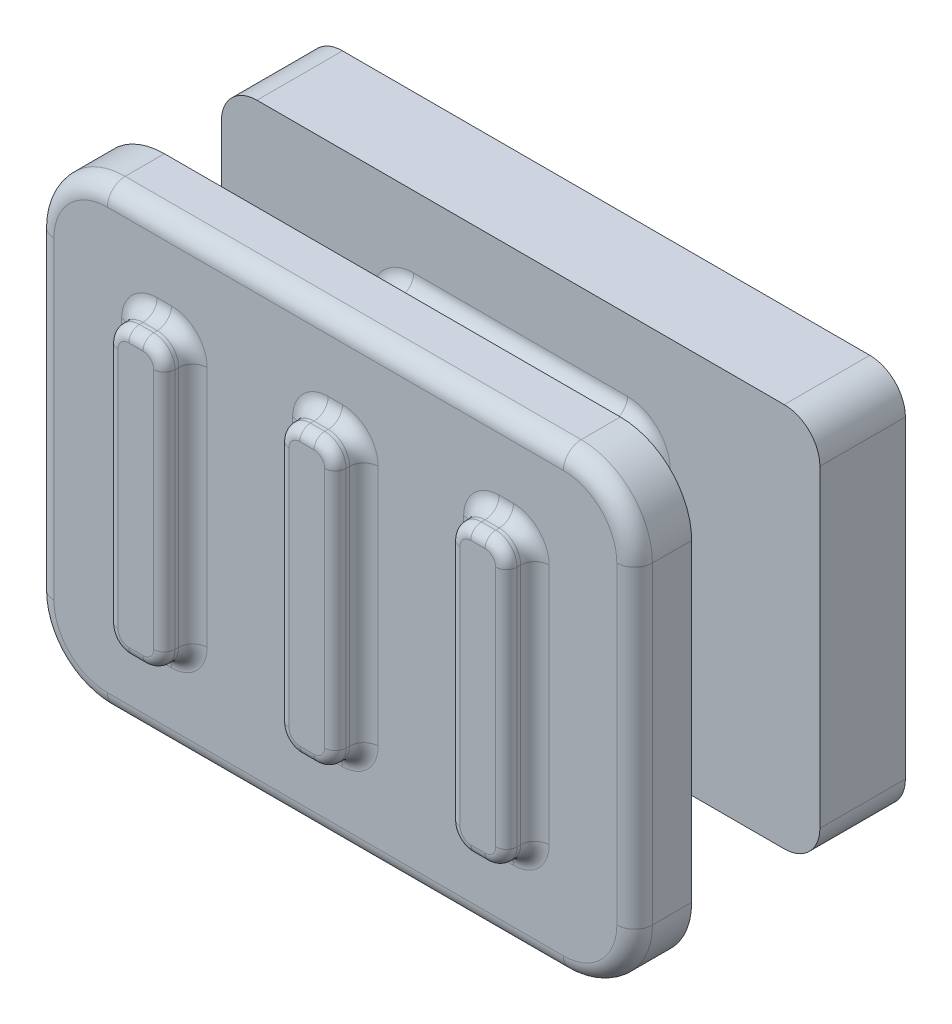
SolidWorks part; units mm, degrees
ref_plane "Спереди" through (0, 0, 0) normal (0, 0, 1) x (1, 0, 0)
ref_plane "Сверху" through (0, 0, 0) normal (0, 1, 0) x (1, 0, 0)
ref_plane "Справа" through (0, 0, 0) normal (1, 0, 0) x (0, 0, -1)
other "Configuration Table"
sketch "Slider_stem_profile" plane through (0, 0, 0) normal (0, 0, 1) x (1, 0, 0)
  line L0 (-1.5, -1.5) -> (1.5, -1.5)
  line L1 (1.9, -1.1) -> (1.9, 1.1)
  line L2 (1.5, 1.5) -> (-1.5, 1.5)
  line L3 (-1.9, 1.1) -> (-1.9, -1.1)
  arc A0 (1.5, -1.5) -> (1.9, -1.1) centre (1.5, -1.1) ccw
  arc A1 (1.9, 1.1) -> (1.5, 1.5) centre (1.5, 1.1) ccw
  arc A2 (-1.5, 1.5) -> (-1.9, 1.1) centre (-1.5, 1.1) ccw
  arc A3 (-1.9, -1.1) -> (-1.5, -1.5) centre (-1.5, -1.1) ccw
extrude "Slider_stem" add sketch "Slider_stem_profile" along normal blind 4.2 from offset 0
sketch "Captive_flange_profile" plane through (0, 0, 0) normal (0, 0, 1) x (1, 0, 0)
  line L0 (-3.7, -2.7) -> (3.7, -2.7)
  line L1 (4.2, -2.2) -> (4.2, 2.2)
  line L2 (3.7, 2.7) -> (-3.7, 2.7)
  line L3 (-4.2, 2.2) -> (-4.2, -2.2)
  arc A0 (3.7, -2.7) -> (4.2, -2.2) centre (3.7, -2.2) ccw
  arc A1 (4.2, 2.2) -> (3.7, 2.7) centre (3.7, 2.2) ccw
  arc A2 (-3.7, 2.7) -> (-4.2, 2.2) centre (-3.7, 2.2) ccw
  arc A3 (-4.2, -2.2) -> (-3.7, -2.7) centre (-3.7, -2.2) ccw
extrude "Captive_flange" add sketch "Captive_flange_profile" along normal blind 1.2 from offset 1.2
sketch "Thumb_pad_profile" plane through (0, 0, 0) normal (0, 0, 1) x (1, 0, 0)
  line L0 (-3.2, -3.2) -> (3.2, -3.2)
  line L1 (4.2, -2.2) -> (4.2, 2.2)
  line L2 (3.2, 3.2) -> (-3.2, 3.2)
  line L3 (-4.2, 2.2) -> (-4.2, -2.2)
  arc A0 (3.2, -3.2) -> (4.2, -2.2) centre (3.2, -2.2) ccw
  arc A1 (4.2, 2.2) -> (3.2, 3.2) centre (3.2, 2.2) ccw
  arc A2 (-3.2, 3.2) -> (-4.2, 2.2) centre (-3.2, 2.2) ccw
  arc A3 (-4.2, -2.2) -> (-3.2, -3.2) centre (-3.2, -2.2) ccw
extrude "Thumb_pad" add sketch "Thumb_pad_profile" along normal blind 0.8 from offset 4.2
sketch "Switch_pin_socket_profile" plane through (0, 0, 0) normal (0, 0, 1) x (1, 0, 0)
  line L0 (-0.8, -0.6) -> (0.8, -0.6)
  line L1 (0.9, -0.5) -> (0.9, 0.5)
  line L2 (0.8, 0.6) -> (-0.8, 0.6)
  line L3 (-0.9, 0.5) -> (-0.9, -0.5)
  arc A0 (0.8, -0.6) -> (0.9, -0.5) centre (0.8, -0.5) ccw
  arc A1 (0.9, 0.5) -> (0.8, 0.6) centre (0.8, 0.5) ccw
  arc A2 (-0.8, 0.6) -> (-0.9, 0.5) centre (-0.8, 0.5) ccw
  arc A3 (-0.9, -0.5) -> (-0.8, -0.6) centre (-0.8, -0.5) ccw
extrude "Switch_pin_socket" cut sketch "Switch_pin_socket_profile" against normal blind 2.4 from offset 2.3
sketch "PCB_edge_relief_profile" plane through (0, 0, 0) normal (0, 0, 1) x (1, 0, 0)
  line L0 (-2, 0.55) -> (2, 0.55)
  line L1 (2, 0.55) -> (2, 1.6)
  line L2 (2, 1.6) -> (-2, 1.6)
  line L3 (-2, 1.6) -> (-2, 0.55)
extrude "PCB_edge_relief" cut sketch "PCB_edge_relief_profile" against normal blind 0.7 from offset 0.6
fillet "Stem_shoulder_round" radius 0.2 24 edges at (1.7828, -1.3828, 1.2) (-1.7828, -1.3828, 1.2) (-1.7828, 1.3828, 1.2) (1.7828, 1.3828, 1.2) (1.7828, -1.3828, 2.4) (-1.7828, -1.3828, 2.4) (-1.7828, 1.3828, 2.4) (1.7828, 1.3828, 2.4) (-1.7828, -1.3828, 4.2) (-1.7828, 1.3828, 4.2) (1.7828, 1.3828, 4.2) (1.7828, -1.3828, 4.2) (0, 1.5, 1.2) (-1.9, 0, 1.2) (0, -1.5, 1.2) (1.9, 0, 1.2) (0, 1.5, 2.4) (-1.9, 0, 2.4) (0, -1.5, 2.4) (1.9, 0, 2.4) (1.9, 0, 4.2) (0, 1.5, 4.2) (-1.9, 0, 4.2) (0, -1.5, 4.2)
sketch "Thumb_rib_0_profile" plane through (0, 0, 0) normal (0, 0, 1) x (1, 0, 0)
  line L0 (-2.5, -2) -> (-2.3, -2)
  line L1 (-2, -1.7) -> (-2, 1.7)
  line L2 (-2.3, 2) -> (-2.5, 2)
  line L3 (-2.8, 1.7) -> (-2.8, -1.7)
  arc A0 (-2.3, -2) -> (-2, -1.7) centre (-2.3, -1.7) ccw
  arc A1 (-2, 1.7) -> (-2.3, 2) centre (-2.3, 1.7) ccw
  arc A2 (-2.5, 2) -> (-2.8, 1.7) centre (-2.5, 1.7) ccw
  arc A3 (-2.8, -1.7) -> (-2.5, -2) centre (-2.5, -1.7) ccw
extrude "Thumb_rib_0" add sketch "Thumb_rib_0_profile" along normal blind 0.5 from offset 4.9
sketch "Thumb_rib_1_profile" plane through (0, 0, 0) normal (0, 0, 1) x (1, 0, 0)
  line L0 (-0.1, -2) -> (0.1, -2)
  line L1 (0.4, -1.7) -> (0.4, 1.7)
  line L2 (0.1, 2) -> (-0.1, 2)
  line L3 (-0.4, 1.7) -> (-0.4, -1.7)
  arc A0 (0.1, -2) -> (0.4, -1.7) centre (0.1, -1.7) ccw
  arc A1 (0.4, 1.7) -> (0.1, 2) centre (0.1, 1.7) ccw
  arc A2 (-0.1, 2) -> (-0.4, 1.7) centre (-0.1, 1.7) ccw
  arc A3 (-0.4, -1.7) -> (-0.1, -2) centre (-0.1, -1.7) ccw
extrude "Thumb_rib_1" add sketch "Thumb_rib_1_profile" along normal blind 0.5 from offset 4.9
sketch "Thumb_rib_2_profile" plane through (0, 0, 0) normal (0, 0, 1) x (1, 0, 0)
  line L0 (2.3, -2) -> (2.5, -2)
  line L1 (2.8, -1.7) -> (2.8, 1.7)
  line L2 (2.5, 2) -> (2.3, 2)
  line L3 (2, 1.7) -> (2, -1.7)
  arc A0 (2.5, -2) -> (2.8, -1.7) centre (2.5, -1.7) ccw
  arc A1 (2.8, 1.7) -> (2.5, 2) centre (2.5, 1.7) ccw
  arc A2 (2.3, 2) -> (2, 1.7) centre (2.3, 1.7) ccw
  arc A3 (2, -1.7) -> (2.3, -2) centre (2.3, -1.7) ccw
extrude "Thumb_rib_2" add sketch "Thumb_rib_2_profile" along normal blind 0.5 from offset 4.9
fillet "Thumb_rib_root_round" radius 0.2 24 edges at (2.0879, -1.9121, 5) (2.4, -2, 5) (2.7121, -1.9121, 5) (2.7121, 1.9121, 5) (2.4, 2, 5) (2.0879, 1.9121, 5) (-0.3121, -1.9121, 5) (0, -2, 5) (0.3121, -1.9121, 5) (0.3121, 1.9121, 5) (0, 2, 5) (-0.3121, 1.9121, 5) (-2.7121, -1.9121, 5) (-2.4, -2, 5) (-2.0879, -1.9121, 5) (-2.0879, 1.9121, 5) (-2.4, 2, 5) (-2.7121, 1.9121, 5) (2.8, 0, 5) (2, 0, 5) (0.4, 0, 5) (-0.4, 0, 5) (-2, 0, 5) (-2.8, 0, 5)
fillet "Thumb_pad_edge_round" radius 0.25 8 edges at (-3.9071, -2.9071, 5) (-4.2, 0, 5) (0, -3.2, 5) (-3.9071, 2.9071, 5) (3.9071, -2.9071, 5) (0, 3.2, 5) (4.2, 0, 5) (3.9071, 2.9071, 5)
fillet "Thumb_rib_crown_round" radius 0.15 24 edges at (2.8, 0, 5.4) (2.7121, 1.9121, 5.4) (2.7121, -1.9121, 5.4) (2.4, 2, 5.4) (2.4, -2, 5.4) (2.0879, 1.9121, 5.4) (2.0879, -1.9121, 5.4) (2, 0, 5.4) (0.4, 0, 5.4) (0.3121, 1.9121, 5.4) (0.3121, -1.9121, 5.4) (0, 2, 5.4) (0, -2, 5.4) (-0.3121, 1.9121, 5.4) (-0.3121, -1.9121, 5.4) (-0.4, 0, 5.4) (-2, 0, 5.4) (-2.0879, 1.9121, 5.4) (-2.0879, -1.9121, 5.4) (-2.4, 2, 5.4) (-2.4, -2, 5.4) (-2.7121, 1.9121, 5.4) (-2.7121, -1.9121, 5.4) (-2.8, 0, 5.4)
